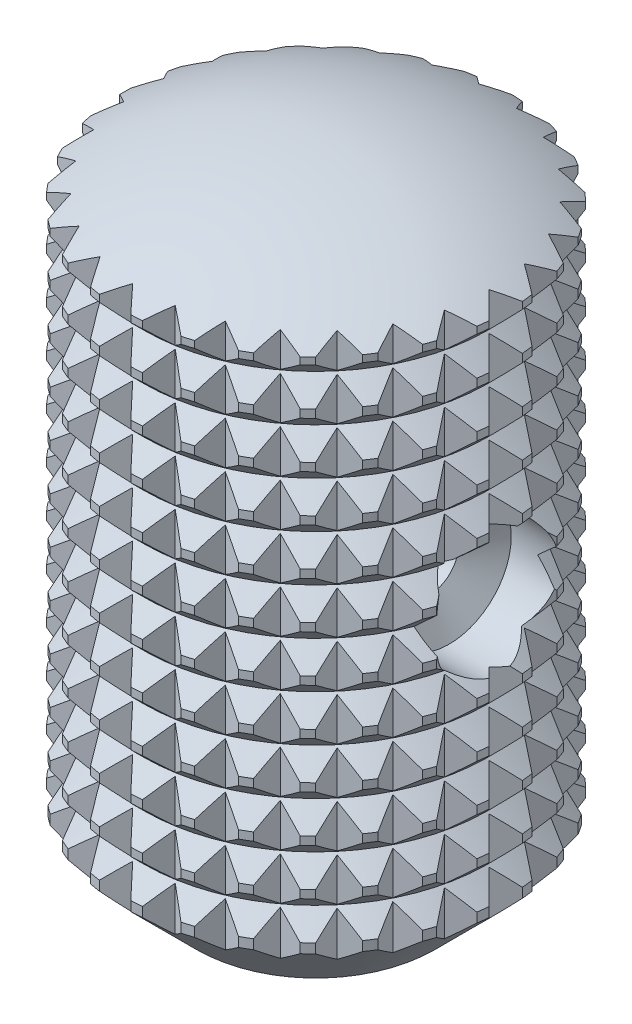
SolidWorks part; units mm, degrees
ref_plane "Front Plane" through (0, 0, 0) normal (0, 0, 1) x (1, 0, 0)
ref_plane "Top Plane" through (0, 0, 0) normal (0, 1, 0) x (1, 0, 0)
ref_plane "Right Plane" through (0, 0, 0) normal (1, 0, 0) x (0, 0, -1)
sketch "Sketch1" plane through (0, 0, 0) normal (0, 1, 0) x (1, 0, 0)
  circle A0 centre (0, 0) radius 4
  dimension "D1" = 8
extrude "Boss-Extrude1" add sketch "Sketch1" along normal mid plane 13.5
chamfer "Chamfer1" distance 1.5 angle 45 1 edges at (0, -6.75, 4)
sketch "Sketch2" plane through (0, 0, 0) normal (0, 0, 1) x (1, 0, 0)
  line L0 (0, 0) -> (0, 6.75) construction
  line L1 (4, 6.75) -> (-4, 6.75) construction
  line L2 (4, -5.25) -> (4, 6.75) construction
  line L3 (0, 6.75) -> (0, 7.75)
  line L4 (0, 7.75) -> (4, 7.75)
  line L5 (4, 5.5943) -> (4, 7.75)
  arc A0 (0, 6.75) -> (4, 5.5943) centre (0, -0.75) cw
  dimension "D1" = 7.5
  dimension "D2" = 1
revolve "Cut-Revolve1" cut sketch "Sketch2" angle 360 about L0
hole_wizard "Ø2.5 (2.5) Diameter Hole1" positions "Sketch6" profile "Sketch5" hole size "Ø2.5" standard "DIN"
sketch "Sketch6" plane through (0, -6.75, 0) normal (0, -1, 0) x (-1, 0, 0)
  point P0 (0, 0)
sketch "Sketch5" plane through (0, -6.75, 0) normal (1, 0, 0) x (0, 0, -1)
  line L0 (0, 0) -> (0, 11.7511)
  line L1 (0, 11.7511) -> (1.25, 11)
  line L2 (1.25, 11) -> (1.25, 0)
  line L5 (1.25, 0) -> (0, 0)
  line L10 (0, 11.7511) -> (-1.25, 11) construction
  line L11 (0, -6.35) -> (0, 107.95) construction
  dimension "Hole Dia." = 2.5
  dimension "Hole Depth" = 11
  dimension "Drill Angle" = 118
ref_plane "Plane1" through (4, 0, 0) normal (1, 0, 0) x (0, 0, -1)
hole_wizard "CSK for M1.4 Countersunk Flat Head Screw1" positions "Sketch8" profile "Sketch9" countersink size "M1.6" standard "DIN" end condition up to next
sketch "Sketch8" plane through (4, 0, 0) normal (1, 0, 0) x (0, 0, -1)
  line L0 (0, 0) -> (0, 6.75) construction
  line L1 (-2.5, -6.75) -> (2.5, -6.75) construction
  point P0 (0, 0.25)
  dimension "D1" = 7
sketch "Sketch9" plane through (4, 0.25, 0) normal (0, 1, 0) x (0, 0, -1)
  line L0 (0, 0) -> (0, 2.75)
  line L1 (0, 2.75) -> (0.6, 2.75)
  line L2 (0.6, 2.75) -> (0.6, 1.6041)
  line L3 (0.6, 1.6041) -> (1.3, 1.2)
  line L4 (1.3, 1.2) -> (1.3, 0)
  line L6 (1.3, 0) -> (0, 0)
  line L7 (-0.6, 1.6041) -> (-1.3, 1.2) construction
  line L11 (0, -6.35) -> (0, 107.95) construction
  dimension "Thru Hole Dia." = 1.2
  dimension "Thru Hole Depth" = 2.75
  dimension "C'Sink Dia." = 2.6
  dimension "C'Sink Angle" = 120
  dimension "Head Clearance" = 1.2
cosmetic thread "Cosmetic Thread1" parameters "D2"=1.4
sketch "Sketch3" plane through (0, 0, 0) normal (0, 0, 1) x (1, 0, 0)
  line L0 (-3.6, -4.65) -> (-4.0824, -4.65) construction
  line L1 (-4, -5.05) -> (-3.6, -4.65)
  line L2 (-3.6, -4.65) -> (-4, -4.25)
  line L3 (-4, 5.5943) -> (-4, -5.25) construction
  line L4 (0, 0) -> (0, -6.75) construction
  line L5 (-4, -4.25) -> (-4, -5.05)
  line L6 (-2.5, -6.75) -> (2.5, -6.75) construction
  dimension "D1" = 0.6
  dimension "D2" = 0.2
revolve "Cut-Revolve2" cut sketch "Sketch3" angle 360 about L4
pattern_linear "LPattern1" count 11 spacing 0.97 along (0, 1, 0) of "Cut-Revolve2"
sketch "Sketch4" plane through (0, 0, 0) normal (0, 1, 0) x (1, 0, 0)
  line L0 (0, 0) -> (4.8902, 0) construction
  line L1 (3.6351, 0) -> (3.9847, 0.3496)
  line L3 (3.6351, 0) -> (3.9847, -0.3496)
  circle A0 centre (0, 0) radius 4 construction
  arc A1 (3.9847, -0.3496) -> (3.9847, 0.3496) centre (0, 0) ccw
  dimension "D1" = 0.7
extrude "Cut-Extrude2" cut sketch "Sketch4" against normal through all both and the other way through all contours L3 A1 L1
pattern_circular "CirPattern2" count 27 over 360 about axis through (0, 5.05, 0) along (0, -1, 0) of "Cut-Extrude2"
